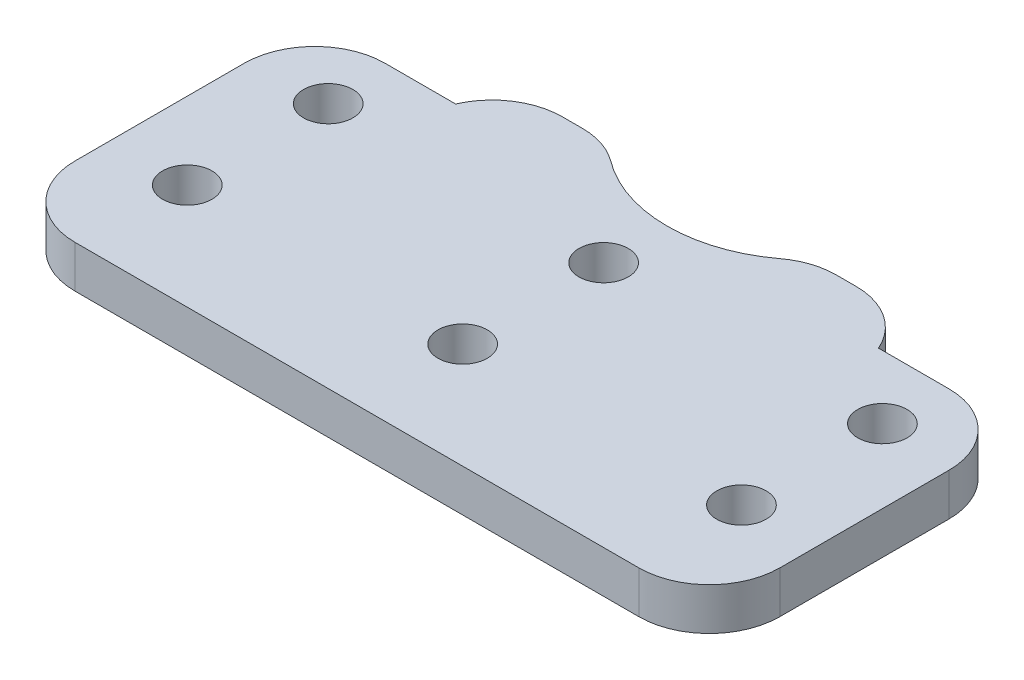
SolidWorks part; units mm, degrees
ref_plane "Front Plane" through (0, 0, 0) normal (0, 0, 1) x (1, 0, 0)
ref_plane "Top Plane" through (0, 0, 0) normal (0, 1, 0) x (1, 0, 0)
ref_plane "Right Plane" through (0, 0, 0) normal (1, 0, 0) x (0, 0, -1)
sketch "Sketch1" plane through (0, 0, 0) normal (0, 1, 0) x (1, 0, 0)
  line L0 (25, 25) -> (25, 17.5) construction
  line L1 (0, 0) -> (50, 0)
  line L2 (0, 0) -> (0, 25)
  line L3 (0, 25) -> (50, 25)
  line L4 (50, 0) -> (50, 25)
  line L5 (25, 17.5) -> (25, 7.5) construction
  line L6 (25, 7.5) -> (25, 0) construction
  line L7 (5.4632, 25) -> (5.4632, 17.5) construction
  line L8 (5.4632, 17.5) -> (5.4632, 7.5) construction
  line L9 (5.4632, 7.5) -> (5.4632, 0) construction
  line L11 (44.7776, 25) -> (44.7776, 17.5) construction
  line L12 (44.7776, 17.5) -> (44.7776, 7.5) construction
  line L13 (44.7776, 7.5) -> (44.7776, 0) construction
  circle A0 centre (25, 17.5) radius 1.75
  circle A1 centre (25, 7.5) radius 1.75
  circle A2 centre (5.4632, 17.5) radius 1.75
  circle A3 centre (5.4632, 7.5) radius 1.75
  circle A4 centre (44.7776, 7.5) radius 1.75
  circle A5 centre (44.7776, 17.5) radius 1.75
  dimension "D3" = 3.5
  dimension "D1" = 50
  dimension "D2" = 25
  dimension "D4" = 10
extrude "Boss-Extrude1" add sketch "Sketch1" along normal blind 3
sketch "Sketch2" plane through (0, 3, 0) normal (0, 1, 0) x (1, 0, 0)
  line L0 (25, 25) -> (25, 32) construction
  line L1 (0, 25) -> (10, 25)
  line L2 (0, 25) -> (0, 22)
  line L3 (0, 22) -> (10, 22)
  line L4 (10, 25) -> (10, 22)
  line L5 (50, 25) -> (40, 25)
  line L6 (50, 25) -> (50, 22)
  line L7 (50, 22) -> (40, 22)
  line L8 (40, 25) -> (40, 22)
  line L9 (50, 25) -> (0, 25) construction
  circle A0 centre (25, 32) radius 10
  dimension "D3" = 20
  dimension "D1" = 10
  dimension "D2" = 3
  dimension "D4" = 7
extrude "Cut-Extrude1" cut sketch "Sketch2" against normal blind 10
fillet "Fillet1" radius 5 8 edges at (50, 1.5, 0) (0, 1.5, 0) (50, 1.5, -22) (40, 1.5, -25) (10, 1.5, -25) (0, 1.5, -22) (32.1414, 1.5, -25) (17.8586, 1.5, -25)
